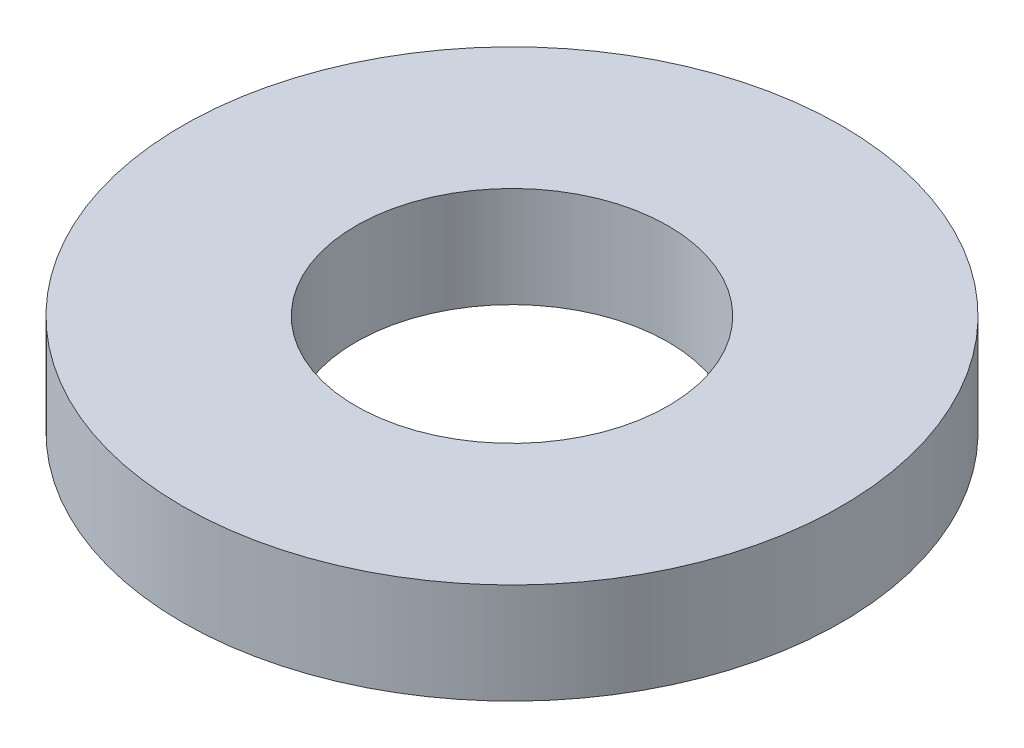
SolidWorks part; units mm, degrees
ref_plane "Front Plane" through (0, 0, 0) normal (0, 0, 1) x (1, 0, 0)
ref_plane "Top Plane" through (0, 0, 0) normal (0, 1, 0) x (1, 0, 0)
ref_plane "Right Plane" through (0, 0, 0) normal (1, 0, 0) x (0, 0, -1)
sketch "Sketch1" plane through (0, 0, 0) normal (0, 1, 0) x (1, 0, 0)
  circle A0 centre (0, 0) radius 95
  dimension "FLANGE_OD" = 190
extrude "Boss-Extrude1" add sketch "Sketch1" along normal blind 29
sketch "Sketch2" plane through (0, 0, 0) normal (0, 1, 0) x (1, 0, 0)
  circle A0 centre (0, 0) radius 45
  dimension "BORE_D" = 90
extrude "Cut-Extrude1" cut sketch "Sketch2" along normal through all
sketch "Sketch3" plane through (0, 29, 0) normal (0, 1, 0) x (1, 0, 0)
  circle A0 centre (0, 0) radius 27.2291 construction
  circle A1 centre (-27.2291, 0) radius 3.67
  dimension "BOLT_D" = 7.3399
  dimension "BOLT_PCD" = 54.4583
extrude "Cut-Extrude2" cut sketch "Sketch3" against normal blind 27.1484 rebuild error yes
pattern_circular "CirPattern1" count 3 over 360 rebuild error yes
